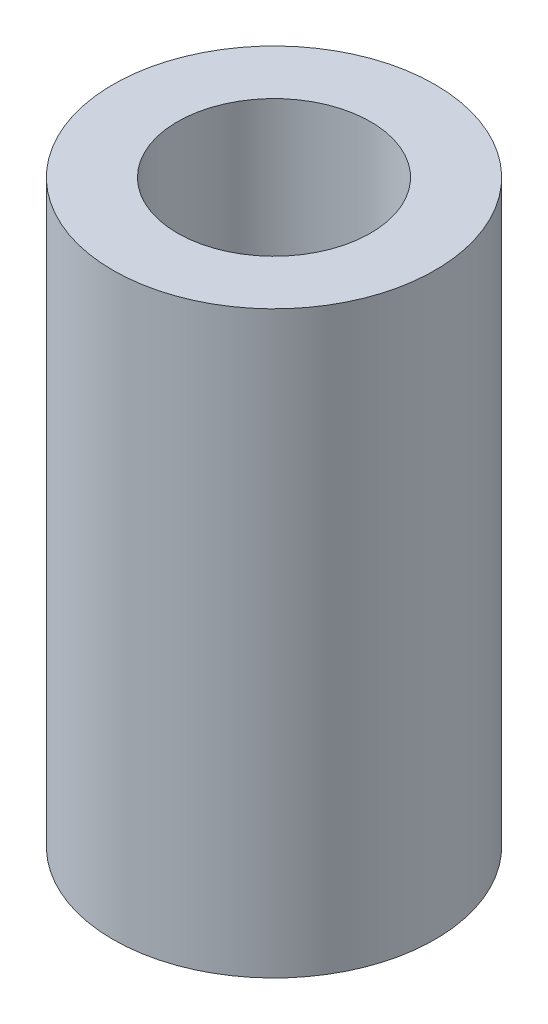
SolidWorks part; units mm, degrees
ref_plane "Front Plane" through (0, 0, 0) normal (0, 0, 1) x (1, 0, 0)
ref_plane "Top Plane" through (0, 0, 0) normal (0, 1, 0) x (1, 0, 0)
ref_plane "Right Plane" through (0, 0, 0) normal (1, 0, 0) x (0, 0, -1)
sketch "Sketch1" plane through (0, 0, 0) normal (0, 1, 0) x (1, 0, 0)
  circle A0 centre (0, 0) radius 1.5
  circle A1 centre (0, 0) radius 2.5
  dimension "D1" = 3
  dimension "D2" = 5
extrude "Boss-Extrude1" add sketch "Sketch1" along normal blind 9
